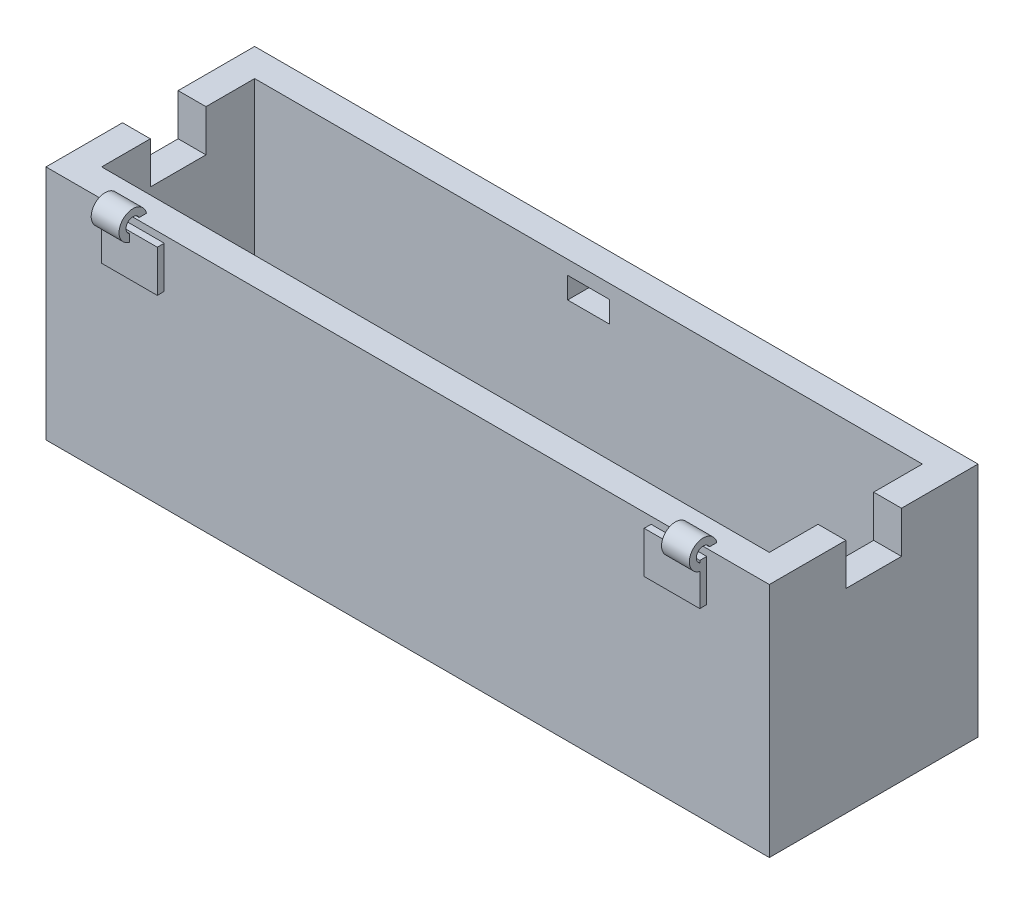
SolidWorks part; units mm, degrees
ref_plane "前基準面" through (0, 0, 0) normal (0, 0, 1) x (1, 0, 0)
ref_plane "上基準面" through (0, 0, 0) normal (0, 1, 0) x (1, 0, 0)
ref_plane "右基準面" through (0, 0, 0) normal (1, 0, 0) x (0, 0, -1)
sketch "草圖1" plane through (0, 0, 0) normal (0, 1, 0) x (1, 0, 0)
  line L1 (-260, 75) -> (260, 75)
  line L2 (-260, 75) -> (-260, -75)
  line L3 (-260, -75) -> (260, -75)
  line L4 (260, 75) -> (260, -75)
  line L5 (-260, 75) -> (260, -75) construction
  line L6 (-260, -75) -> (260, 75) construction
  point P0 (0, 0)
  dimension "D1" = 520
  dimension "D2" = 150
extrude "填料-伸長1" add sketch "草圖1" along normal blind 140
sketch "草圖2" plane through (0, 140, 0) normal (0, 1, 0) x (1, 0, 0)
  line L0 (260, 75) -> (-260, 75) construction
  line L1 (-240, 55) -> (240, 55)
  line L2 (-240, 55) -> (-240, -55)
  line L3 (-240, -55) -> (240, -55)
  line L4 (240, 55) -> (240, -55)
  line L5 (-240, 55) -> (240, -55) construction
  line L6 (-240, -55) -> (240, 55) construction
  line L7 (-260, 75) -> (-260, -75) construction
  point P0 (0, 0)
  dimension "D1" = 20
  dimension "D2" = 20
extrude "除料-伸長1" cut sketch "草圖2" against normal blind 120
ref_plane "平面1" through (0, 0, 80) normal (0, 0, 1) x (1, 0, 0)
sketch "草圖4" plane through (0, 0, 80) normal (0, 0, 1) x (1, 0, 0)
  line L0 (-260, 140) -> (-260, 0) construction
  line L1 (-215, 135) -> (-175, 135)
  line L2 (-215, 135) -> (-215, 105)
  line L3 (-215, 105) -> (-175, 105)
  line L4 (-175, 135) -> (-175, 105)
  line L5 (-215, 135) -> (-175, 105) construction
  line L6 (-215, 105) -> (-175, 135) construction
  line L7 (-260, 140) -> (260, 140) construction
  point P0 (-195, 120)
  dimension "D1" = 45
  dimension "D2" = 5
  dimension "D3" = 30
  dimension "D4" = 40
extrude "填料-伸長2" add sketch "草圖4" against normal blind 30
sketch "草圖5" plane through (0, 0, 80) normal (0, 0, 1) x (1, 0, 0)
  line L0 (-260, 140) -> (260, 140) construction
  line L1 (175, 135) -> (215, 135)
  line L2 (175, 135) -> (175, 105)
  line L3 (175, 105) -> (215, 105)
  line L4 (215, 135) -> (215, 105)
  line L5 (175, 135) -> (215, 105) construction
  line L6 (175, 105) -> (215, 135) construction
  line L7 (260, 140) -> (260, 0) construction
  point P0 (195, 120)
  dimension "D1" = 5
  dimension "D2" = 45
  dimension "D3" = 40
  dimension "D4" = 30
extrude "填料-伸長3" add sketch "草圖5" against normal blind 30
sketch "草圖7" plane through (215, 0, 0) normal (1, 0, 0) x (0, 0, -1)
  line L0 (-77.5, -865) -> (-77.5, 49135) construction
  line L1 (-75, 135) -> (-80, 135) construction
  line L2 (-1070, 137.7646) -> (48930, 137.7646) construction
  circle A0 centre (-77.5, 137.7646) radius 5
  point P5 (-77.5, 135)
  dimension "D1" = 10
extrude "伸長-薄件1" add sketch "草圖7" against normal blind 20 thin thin type one direction wall 5
sketch "草圖9" plane through (-215, 0, 0) normal (-1, 0, 0) x (0, 0, 1)
  line L0 (77.5, -865) -> (77.5, 49135) construction
  line L1 (75, 135) -> (80, 135) construction
  line L2 (-930, 137.7646) -> (49070, 137.7646) construction
  circle A1 centre (77.5, 137.7646) radius 5
  point P5 (77.5, 135)
extrude "伸長-薄件2" add sketch "草圖9" against normal blind 20 thin thin type one direction wall 5
sketch "草圖11" plane through (-260, 0, 0) normal (-1, 0, 0) x (0, 0, 1)
  line L0 (-75, 140) -> (75, 140) construction
  line L1 (-20, 140) -> (20, 140)
  line L2 (-20, 140) -> (-20, 110)
  line L3 (-20, 110) -> (20, 110)
  line L4 (20, 140) -> (20, 110)
  line L5 (-75, 140) -> (-75, 0) construction
  dimension "D1" = 40
  dimension "D2" = 30
  dimension "D3" = 55
extrude "除料-伸長3" cut sketch "草圖11" against normal through all
sketch "草圖13" plane through (0, 0, 0) normal (0, -1, 0) x (1, 0, 0)
  line L1 (-260, -75) -> (260, -75)
  line L2 (-260, -75) -> (-260, 75)
  line L3 (-260, 75) -> (260, 75)
  line L4 (260, -75) -> (260, 75)
extrude "填料-伸長6" add sketch "草圖13" along normal blind 30
sketch "草圖14" plane through (0, 135, 0) normal (0, 1, 0) x (1, 0, 0)
  line L1 (215, -50) -> (175, -50)
  line L2 (215, -50) -> (215, -55)
  line L3 (215, -55) -> (175, -55)
  line L4 (175, -50) -> (175, -55)
extrude "除料-伸長6" cut sketch "草圖14" against normal blind 30
sketch "草圖15" plane through (0, 135, 0) normal (0, 1, 0) x (1, 0, 0)
  line L1 (-175, -50) -> (-215, -50)
  line L2 (-175, -50) -> (-175, -55)
  line L3 (-175, -55) -> (-215, -55)
  line L4 (-215, -50) -> (-215, -55)
extrude "除料-伸長7" cut sketch "草圖15" against normal blind 30
sketch "草圖18" plane through (0, 0, -75) normal (0, 0, -1) x (-1, 0, 0)
  line L0 (-260, 140) -> (-260, -30) construction
  line L1 (-15, 130) -> (15, 130)
  line L2 (-15, 130) -> (-15, 114.647)
  line L3 (-15, 114.647) -> (15, 114.647)
  line L4 (15, 130) -> (15, 114.647)
  line L5 (-15, 130) -> (15, 114.647) construction
  line L6 (-15, 114.647) -> (15, 130) construction
  line L7 (260, 140) -> (260, -30) construction
  line L8 (-260, 140) -> (260, 140) construction
  point P0 (0, 122.3235)
  dimension "D1" = 245
  dimension "D2" = 245
  dimension "D3" = 10
extrude "除料-伸長8" cut sketch "草圖18" against normal blind 30
fillet "圓角1" radius 10 1 edges at (0, 130, -75)
ref_plane "平面2" through (-225, 0, 0) normal (-1, 0, 0) x (0, 0, 1)
